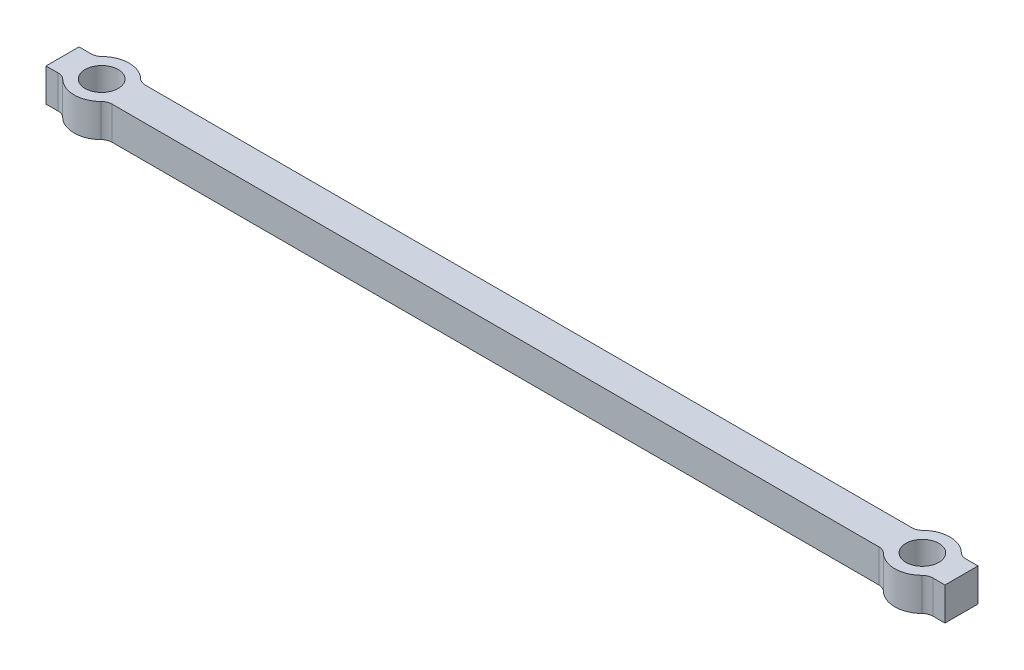
SolidWorks part; units mm, degrees
ref_plane "Front Plane" through (0, 0, 0) normal (0, 0, 1) x (1, 0, 0)
ref_plane "Top Plane" through (0, 0, 0) normal (0, 1, 0) x (1, 0, 0)
ref_plane "Right Plane" through (0, 0, 0) normal (1, 0, 0) x (0, 0, -1)
sketch "Sketch1" plane through (0, 0, 0) normal (0, 1, 0) x (1, 0, 0)
  line L0 (-39.5, 2.5) -> (-39.5, -2.5) construction
  line L1 (-40.8, 2.5) -> (40.8, 2.5)
  line L2 (-40.8, 2.5) -> (-40.8, -2.5)
  line L3 (-40.8, -2.5) -> (40.8, -2.5)
  line L4 (40.8, 2.5) -> (40.8, -2.5)
  line L5 (-40.8, 2.5) -> (40.8, -2.5) construction
  line L6 (-40.8, -2.5) -> (40.8, 2.5) construction
  line L7 (-37.25, 2.5) -> (-37.25, -2.5) construction
  line L8 (-40.8, 0) -> (40.8, 0) construction
  line L9 (0, 2.5) -> (0, -2.5) construction
  line L11 (40.8, 1.5) -> (-40.8, 1.5)
  line L12 (40.8, 1.5) -> (40.8, -1.5)
  line L13 (40.8, -1.5) -> (-40.8, -1.5)
  line L14 (-40.8, 1.5) -> (-40.8, -1.5)
  line L15 (40.8, 1.5) -> (-40.8, -1.5) construction
  line L16 (40.8, -1.5) -> (-40.8, 1.5) construction
  circle A0 centre (-37.25, 0) radius 1.5
  circle A1 centre (-37.25, 0) radius 2.5
  circle A2 centre (37.25, 0) radius 1.5
  circle A3 centre (37.25, 0) radius 2.5
  point P0 (0, 0)
  point P17 (0, 0)
  dimension "D5" = 3
  dimension "D1" = 81.6
  dimension "D2" = 5
  dimension "D3" = 1.3
  dimension "D4" = 2.25
extrude "Shape" add sketch "Sketch1" along normal blind 3 contours L11 A3 L13 L4 | A3 L11 A2 L13 | A3 L13 | A3 L11 | A3 L13 A2 L11 | L13 A3 L11 A1 | L13 A1 L11 A0 | L11 A1 | L11 A1 L13 A0 | A1 L13 | A1 L11 L2 L13 region at (-37.25, 0, -1.9078) region at (-40.1864, 0, 0) region at (37.25, 0, -1.9078) region at (-35.5296, 0, 0) region at (0, 0, 0) region at (-38.9704, 0, 0) region at (38.9704, 0, 0) region at (40.1864, 0, 0) region at (35.5296, 0, 0) region at (-37.25, 0, 1.9078) region at (37.25, 0, 1.9078)
fillet "Mill fillets" radius 1 8 edges at (39.25, 1.5, -1.5) (-35.25, 1.5, -1.5) (-39.25, 1.5, -1.5) (35.25, 1.5, -1.5) (-39.25, 1.5, 1.5) (35.25, 1.5, 1.5) (39.25, 1.5, 1.5) (-35.25, 1.5, 1.5)
